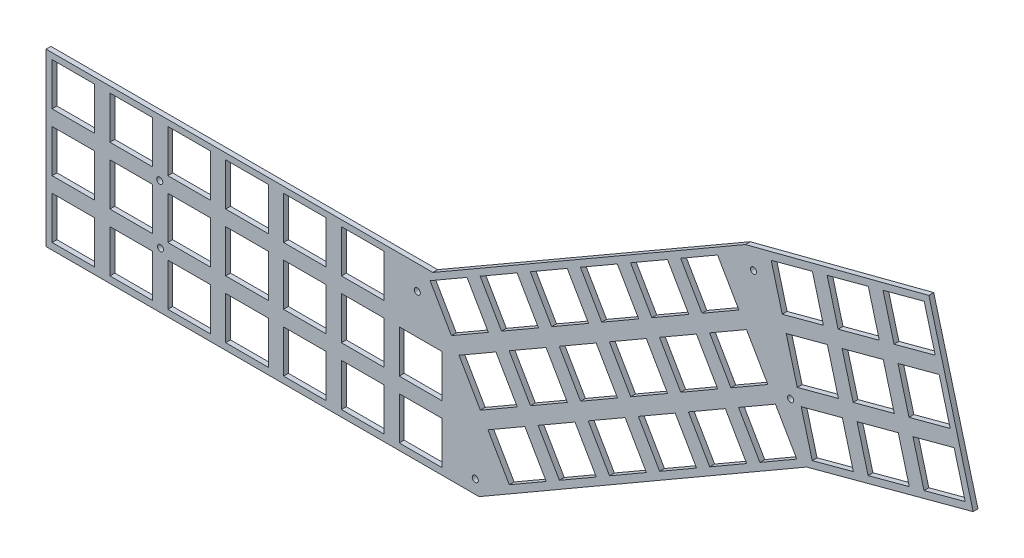
SolidWorks part; units mm, degrees
ref_plane "Plan de face" through (0, 0, 0) normal (0, 0, 1) x (1, 0, 0)
ref_plane "Plan de dessus" through (0, 0, 0) normal (0, 1, 0) x (1, 0, 0)
ref_plane "Plan de droite" through (0, 0, 0) normal (1, 0, 0) x (0, 0, -1)
sketch "Model" plane through (0, 0, 0) normal (0, 0, 1) x (1, 0, 0)
  line L0 (152.8114, 25.9717) -> (138.2826, 80.2215)
  line L1 (98.1506, 11.3316) -> (152.8114, 25.9717)
  line L2 (-9.3986, -50.8585) -> (98.1506, 11.3316)
  line L3 (-151.6088, -50.8585) -> (-9.3986, -50.8585)
  line L4 (-24.5886, 5.3017) -> (-151.6088, 5.2929)
  line L5 (78.0109, 64.5416) -> (-24.5886, 5.3017)
  line L6 (138.2826, 80.2215) -> (78.0109, 64.5416)
  line L7 (-151.6088, 5.2929) -> (-151.6088, -50.8585)
  line L8 (-54.6088, -34.6876) -> (-54.6088, -48.6876)
  line L9 (-54.6088, -48.6876) -> (-40.6088, -48.6876)
  line L10 (-40.6088, -34.6876) -> (-40.6088, -48.6876)
  line L11 (-54.6088, -34.6876) -> (-40.6088, -34.6876)
  line L12 (-35.6088, -34.6876) -> (-35.6088, -48.6876)
  line L13 (-35.6088, -48.6876) -> (-21.6088, -48.6876)
  line L14 (-21.6088, -34.6876) -> (-21.6088, -48.6876)
  line L15 (-35.6088, -34.6876) -> (-21.6088, -34.6876)
  line L16 (-35.6088, -15.6876) -> (-35.6088, -29.6876)
  line L17 (-35.6088, -29.6876) -> (-21.6088, -29.6876)
  line L18 (-21.6088, -15.6876) -> (-21.6088, -29.6876)
  line L19 (-35.6088, -15.6876) -> (-21.6088, -15.6876)
  line L20 (-54.6088, -15.6876) -> (-54.6088, -29.6876)
  line L21 (-54.6088, -29.6876) -> (-40.6088, -29.6876)
  line L22 (-40.6088, -15.6876) -> (-40.6088, -29.6876)
  line L23 (-54.6088, -15.6876) -> (-40.6088, -15.6876)
  line L24 (-54.6088, 3.3124) -> (-54.6088, -10.6876)
  line L25 (-54.6088, -10.6876) -> (-40.6088, -10.6876)
  line L26 (-40.6088, 3.3124) -> (-40.6088, -10.6876)
  line L27 (-54.6088, 3.3124) -> (-40.6088, 3.3124)
  line L28 (-73.6088, -34.6876) -> (-73.6088, -48.6876)
  line L29 (-73.6088, -48.6876) -> (-59.6088, -48.6876)
  line L30 (-59.6088, -34.6876) -> (-59.6088, -48.6876)
  line L31 (-73.6088, -34.6876) -> (-59.6088, -34.6876)
  line L32 (-73.6088, -15.6876) -> (-73.6088, -29.6876)
  line L33 (-73.6088, -29.6876) -> (-59.6088, -29.6876)
  line L34 (-59.6088, -15.6876) -> (-59.6088, -29.6876)
  line L35 (-73.6088, -15.6876) -> (-59.6088, -15.6876)
  line L36 (-73.6088, 3.3124) -> (-73.6088, -10.6876)
  line L37 (-73.6088, -10.6876) -> (-59.6088, -10.6876)
  line L38 (-59.6088, 3.3124) -> (-59.6088, -10.6876)
  line L39 (-73.6088, 3.3124) -> (-59.6088, 3.3124)
  line L40 (-92.6088, -34.6876) -> (-92.6088, -48.6876)
  line L41 (-92.6088, -48.6876) -> (-78.6088, -48.6876)
  line L42 (-78.6088, -34.6876) -> (-78.6088, -48.6876)
  line L43 (-92.6088, -34.6876) -> (-78.6088, -34.6876)
  line L44 (-92.6088, -15.6876) -> (-92.6088, -29.6876)
  line L45 (-92.6088, -29.6876) -> (-78.6088, -29.6876)
  line L46 (-78.6088, -15.6876) -> (-78.6088, -29.6876)
  line L47 (-92.6088, -15.6876) -> (-78.6088, -15.6876)
  line L48 (-92.6088, 3.3124) -> (-92.6088, -10.6876)
  line L49 (-92.6088, -10.6876) -> (-78.6088, -10.6876)
  line L50 (-78.6088, 3.3124) -> (-78.6088, -10.6876)
  line L51 (-92.6088, 3.3124) -> (-78.6088, 3.3124)
  line L52 (-111.6088, -34.6876) -> (-111.6088, -48.6876)
  line L53 (-111.6088, -48.6876) -> (-97.6088, -48.6876)
  line L54 (-97.6088, -34.6876) -> (-97.6088, -48.6876)
  line L55 (-111.6088, -34.6876) -> (-97.6088, -34.6876)
  line L56 (-111.6088, -15.6876) -> (-111.6088, -29.6876)
  line L57 (-111.6088, -29.6876) -> (-97.6088, -29.6876)
  line L58 (-97.6088, -15.6876) -> (-97.6088, -29.6876)
  line L59 (-111.6088, -15.6876) -> (-97.6088, -15.6876)
  line L60 (-130.6088, -34.6876) -> (-130.6088, -48.6876)
  line L61 (-130.6088, -48.6876) -> (-116.6088, -48.6876)
  line L62 (-116.6088, -34.6876) -> (-116.6088, -48.6876)
  line L63 (-130.6088, -34.6876) -> (-116.6088, -34.6876)
  line L64 (-130.6088, -15.6876) -> (-130.6088, -29.6876)
  line L65 (-130.6088, -29.6876) -> (-116.6088, -29.6876)
  line L66 (-116.6088, -15.6876) -> (-116.6088, -29.6876)
  line L67 (-130.6088, -15.6876) -> (-116.6088, -15.6876)
  line L68 (-149.6088, -34.6876) -> (-149.6088, -48.6876)
  line L69 (-149.6088, -48.6876) -> (-135.6088, -48.6876)
  line L70 (-135.6088, -34.6876) -> (-135.6088, -48.6876)
  line L71 (-149.6088, -34.6876) -> (-135.6088, -34.6876)
  line L72 (-149.6088, -15.6876) -> (-149.6088, -29.6876)
  line L73 (-149.6088, -29.6876) -> (-135.6088, -29.6876)
  line L74 (-135.6088, -15.6876) -> (-135.6088, -29.6876)
  line L75 (-149.6088, -15.6876) -> (-135.6088, -15.6876)
  line L76 (-111.6088, 3.3124) -> (-111.6088, -10.6876)
  line L77 (-111.6088, -10.6876) -> (-97.6088, -10.6876)
  line L78 (-97.6088, 3.3124) -> (-97.6088, -10.6876)
  line L79 (-111.6088, 3.3124) -> (-97.6088, 3.3124)
  line L80 (-130.6088, 3.3124) -> (-130.6088, -10.6876)
  line L81 (-130.6088, -10.6876) -> (-116.6088, -10.6876)
  line L82 (-116.6088, 3.3124) -> (-116.6088, -10.6876)
  line L83 (-130.6088, 3.3124) -> (-116.6088, 3.3124)
  line L84 (-149.6088, 3.3124) -> (-149.6088, -10.6876)
  line L85 (-149.6088, -10.6876) -> (-135.6088, -10.6876)
  line L86 (-135.6088, 3.3124) -> (-135.6088, -10.6876)
  line L87 (-149.6088, 3.3124) -> (-135.6088, 3.3124)
  line L88 (96.3487, 27.5969) -> (99.9722, 14.074)
  line L89 (99.9722, 14.074) -> (113.4951, 17.6974)
  line L90 (109.8717, 31.2204) -> (113.4951, 17.6974)
  line L91 (96.3487, 27.5969) -> (109.8717, 31.2204)
  line L92 (91.4311, 45.9495) -> (95.0546, 32.4266)
  line L93 (95.0546, 32.4266) -> (108.5776, 36.05)
  line L94 (104.9541, 49.573) -> (108.5776, 36.05)
  line L95 (91.4311, 45.9495) -> (104.9541, 49.573)
  line L96 (109.7837, 50.8671) -> (113.4072, 37.3441)
  line L97 (113.4072, 37.3441) -> (126.9302, 40.9676)
  line L98 (123.3067, 54.4906) -> (126.9302, 40.9676)
  line L99 (109.7837, 50.8671) -> (123.3067, 54.4906)
  line L100 (114.7013, 32.5145) -> (118.3248, 18.9915)
  line L101 (118.3248, 18.9915) -> (131.8477, 22.615)
  line L102 (128.2243, 36.138) -> (131.8477, 22.615)
  line L103 (114.7013, 32.5145) -> (128.2243, 36.138)
  line L104 (133.0539, 37.4321) -> (136.6774, 23.9091)
  line L105 (136.6774, 23.9091) -> (150.2003, 27.5326)
  line L106 (146.5768, 41.0555) -> (150.2003, 27.5326)
  line L107 (133.0539, 37.4321) -> (146.5768, 41.0555)
  line L108 (128.1363, 55.7847) -> (131.7598, 42.2617)
  line L109 (131.7598, 42.2617) -> (145.2828, 45.8852)
  line L110 (141.6593, 59.4081) -> (145.2828, 45.8852)
  line L111 (128.1363, 55.7847) -> (141.6593, 59.4081)
  line L112 (123.2188, 74.1372) -> (126.8422, 60.6143)
  line L113 (126.8422, 60.6143) -> (140.3652, 64.2378)
  line L114 (136.7417, 77.7607) -> (140.3652, 64.2378)
  line L115 (123.2188, 74.1372) -> (136.7417, 77.7607)
  line L116 (104.8662, 69.2197) -> (108.4896, 55.6967)
  line L117 (108.4896, 55.6967) -> (122.0126, 59.3202)
  line L118 (118.3891, 72.8432) -> (122.0126, 59.3202)
  line L119 (104.8662, 69.2197) -> (118.3891, 72.8432)
  line L120 (86.5136, 64.3021) -> (90.137, 50.7792)
  line L121 (90.137, 50.7792) -> (103.66, 54.4026)
  line L122 (100.0365, 67.9256) -> (103.66, 54.4026)
  line L123 (86.5136, 64.3021) -> (100.0365, 67.9256)
  line L124 (87.902, 24.0982) -> (94.902, 11.9739)
  line L125 (94.902, 11.9739) -> (82.7777, 4.9739)
  line L126 (75.7777, 17.0982) -> (82.7777, 4.9739)
  line L127 (87.902, 24.0982) -> (75.7777, 17.0982)
  line L128 (78.402, 40.5527) -> (85.402, 28.4283)
  line L129 (85.402, 28.4283) -> (73.2777, 21.4283)
  line L130 (66.2777, 33.5527) -> (73.2777, 21.4283)
  line L131 (78.402, 40.5527) -> (66.2777, 33.5527)
  line L132 (68.902, 57.0072) -> (75.902, 44.8828)
  line L133 (75.902, 44.8828) -> (63.7777, 37.8828)
  line L134 (56.7777, 50.0072) -> (63.7777, 37.8828)
  line L135 (68.902, 57.0072) -> (56.7777, 50.0072)
  line L136 (71.4475, 14.5982) -> (78.4475, 2.4739)
  line L137 (78.4475, 2.4739) -> (66.3232, -4.5261)
  line L138 (59.3232, 7.5982) -> (66.3232, -4.5261)
  line L139 (71.4475, 14.5982) -> (59.3232, 7.5982)
  line L140 (61.9475, 31.0527) -> (68.9475, 18.9283)
  line L141 (68.9475, 18.9283) -> (56.8232, 11.9283)
  line L142 (49.8232, 24.0527) -> (56.8232, 11.9283)
  line L143 (61.9475, 31.0527) -> (49.8232, 24.0527)
  line L144 (52.4475, 47.5072) -> (59.4475, 35.3828)
  line L145 (59.4475, 35.3828) -> (47.3232, 28.3828)
  line L146 (40.3232, 40.5072) -> (47.3232, 28.3828)
  line L147 (52.4475, 47.5072) -> (40.3232, 40.5072)
  line L148 (54.9931, 5.0982) -> (61.9931, -7.0261)
  line L149 (61.9931, -7.0261) -> (49.8687, -14.0261)
  line L150 (42.8687, -1.9018) -> (49.8687, -14.0261)
  line L151 (54.9931, 5.0982) -> (42.8687, -1.9018)
  line L152 (45.4931, 21.5527) -> (52.4931, 9.4283)
  line L153 (52.4931, 9.4283) -> (40.3687, 2.4283)
  line L154 (33.3687, 14.5527) -> (40.3687, 2.4283)
  line L155 (45.4931, 21.5527) -> (33.3687, 14.5527)
  line L156 (38.5386, -4.4018) -> (45.5386, -16.5261)
  line L157 (45.5386, -16.5261) -> (33.4142, -23.5261)
  line L158 (26.4142, -11.4018) -> (33.4142, -23.5261)
  line L159 (38.5386, -4.4018) -> (26.4142, -11.4018)
  line L160 (29.0386, 12.0527) -> (36.0386, -0.0717)
  line L161 (36.0386, -0.0717) -> (23.9142, -7.0717)
  line L162 (16.9142, 5.0527) -> (23.9142, -7.0717)
  line L163 (29.0386, 12.0527) -> (16.9142, 5.0527)
  line L164 (35.9931, 38.0072) -> (42.9931, 25.8828)
  line L165 (42.9931, 25.8828) -> (30.8687, 18.8828)
  line L166 (23.8687, 31.0072) -> (30.8687, 18.8828)
  line L167 (35.9931, 38.0072) -> (23.8687, 31.0072)
  line L168 (19.5386, 28.5072) -> (26.5386, 16.3828)
  line L169 (26.5386, 16.3828) -> (14.4142, 9.3828)
  line L170 (7.4142, 21.5072) -> (14.4142, 9.3828)
  line L171 (19.5386, 28.5072) -> (7.4142, 21.5072)
  line L172 (3.0841, 19.0072) -> (10.0841, 6.8828)
  line L173 (10.0841, 6.8828) -> (-2.0403, -0.1172)
  line L174 (-9.0403, 12.0072) -> (-2.0403, -0.1172)
  line L175 (3.0841, 19.0072) -> (-9.0403, 12.0072)
  line L176 (12.5841, 2.5527) -> (19.5841, -9.5717)
  line L177 (19.5841, -9.5717) -> (7.4597, -16.5717)
  line L178 (0.4597, -4.4473) -> (7.4597, -16.5717)
  line L179 (12.5841, 2.5527) -> (0.4597, -4.4473)
  line L180 (22.0841, -13.9018) -> (29.0841, -26.0261)
  line L181 (29.0841, -26.0261) -> (16.9597, -33.0261)
  line L182 (9.9597, -20.9018) -> (16.9597, -33.0261)
  line L183 (22.0841, -13.9018) -> (9.9597, -20.9018)
  line L184 (5.6296, -23.4018) -> (12.6296, -35.5261)
  line L185 (12.6296, -35.5261) -> (0.5053, -42.5261)
  line L186 (-6.4947, -30.4018) -> (0.5053, -42.5261)
  line L187 (5.6296, -23.4018) -> (-6.4947, -30.4018)
  line L188 (-3.8704, -6.9473) -> (3.1296, -19.0717)
  line L189 (3.1296, -19.0717) -> (-8.9947, -26.0717)
  line L190 (-15.9947, -13.9473) -> (-8.9947, -26.0717)
  line L191 (-3.8704, -6.9473) -> (-15.9947, -13.9473)
  line L192 (-13.3704, 9.5072) -> (-25.4947, 2.5072)
  line L193 (-25.4947, 2.5072) -> (-18.4947, -9.6172)
  line L194 (-6.3704, -2.6172) -> (-18.4947, -9.6172)
  line L195 (-13.3704, 9.5072) -> (-6.3704, -2.6172)
  circle A0 centre (80.6856, 58.4893) radius 1
  circle A1 centre (92.8776, 28.0855) radius 1
  circle A2 centre (-29.7028, -2.6485) radius 1
  circle A3 centre (-10.6528, -46.4381) radius 1
  circle A4 centre (-114.2594, -13.4181) radius 1
  circle A5 centre (-114.0308, -32.4935) radius 1
extrude "Boss.-Extru.1" add sketch "Model" along normal blind 1.6
